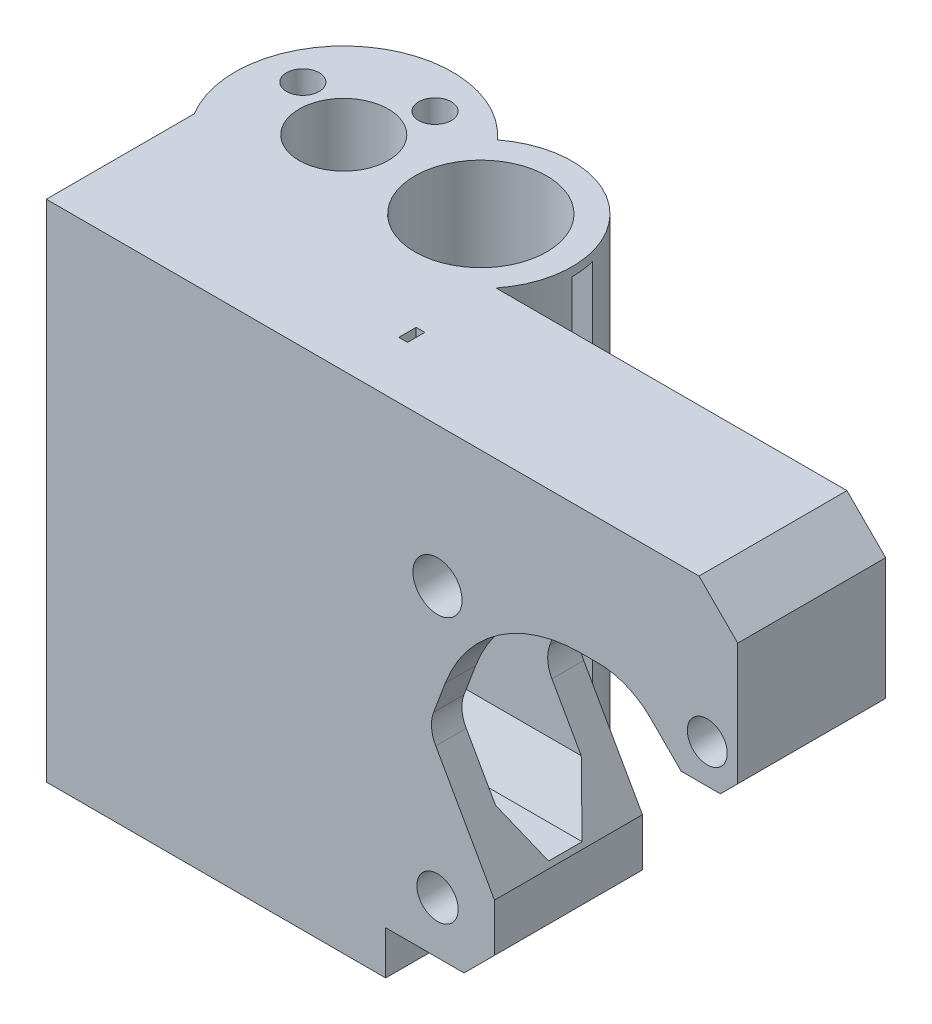
SolidWorks part; units mm, degrees
ref_plane "Front Plane" through (0, 0, 0) normal (0, 0, 1) x (1, 0, 0)
ref_plane "Top Plane" through (0, 0, 0) normal (0, 1, 0) x (1, 0, 0)
ref_plane "Right Plane" through (0, 0, 0) normal (1, 0, 0) x (0, 0, -1)
sketch "Sketch1" plane through (0, 0, 0) normal (0, 0, 1) x (1, 0, 0)
  line L0 (39, -53) -> (48, -53)
  line L1 (0, 0) -> (39, 0)
  line L2 (0, 0) -> (0, -58)
  line L3 (0, -58) -> (39, -58)
  line L4 (39, -53) -> (39, -58)
  line L5 (39, 0) -> (75, 0)
  line L6 (75, 0) -> (79.45, -4.45)
  line L7 (79.45, -4.45) -> (79.45, -18.45)
  line L8 (79.45, -18.45) -> (77.45, -20.45)
  line L9 (77.45, -20.45) -> (72.95, -20.45)
  line L10 (72.95, -20.45) -> (69.45, -16.95)
  line L12 (45.8405, -25.2376) -> (44.5009, -28.8048)
  line L13 (44.75, -32.0294) -> (51.5, -44)
  line L14 (51.5, -44) -> (51.5, -49.5)
  line L15 (61.4145, -14.45) -> (63.4145, -14.45)
  line L16 (51.5, -49.5) -> (48, -53)
  arc A5 (63.4145, -14.45) -> (69.45, -16.95) centre (63.4145, -22.9855) cw
  arc A6 (61.4145, -14.45) -> (45.8405, -25.2376) centre (61.4145, -31.0859) ccw
  arc A7 (44.5009, -28.8048) -> (44.75, -32.0294) centre (48.083, -30.15) ccw
  dimension "D1" = 58
  dimension "D2" = 39
  dimension "D3" = 75
  dimension "D4" = 4.45
  dimension "D5" = 135
  dimension "D6" = 14
  dimension "D7" = 2
  dimension "D8" = 3.5
  dimension "D9" = 6
  dimension "D10" = 5
  dimension "D11" = 4.5
  dimension "D12" = 130
  dimension "D13" = 3.5
  dimension "D14" = 5.5
  dimension "D15" = 6.75
  dimension "D16" = 9
  dimension "D17" = 13.85
  dimension "D18" = 3.417
  dimension "D19" = 2
extrude "Boss-Extrude1" add sketch "Sketch1" along normal blind 17
sketch "Sketch2" plane through (0, 0, 0) normal (0, 1, 0) x (1, 0, 0)
  line L0 (0, -17) -> (0, 6.5) construction
  line L1 (0, 6.5) -> (26.427, 6.5) construction
  circle A0 centre (26.427, 6.5) radius 10.5
  dimension "D2" = 21
  dimension "D1" = 23.5
  dimension "D3" = 26.427
extrude "Boss-Extrude2" add sketch "Sketch2" against normal up to surface (58 mm away) up to face at (19.5, -58, 8.5)
sketch "Sketch3" plane through (0, 0, 0) normal (0, 1, 0) x (1, 0, 0)
  line L0 (0, -17) -> (0, 20.4292) construction
  line L1 (10.6771, 6.5) -> (0, 6.5) construction
  line L2 (75, -17) -> (0, -17) construction
  circle A0 centre (10.6771, 6.5) radius 12.5
  dimension "D3" = 25
  dimension "D2" = 23.5
extrude "Boss-Extrude3" add sketch "Sketch3" against normal blind 13.5
sketch "Sketch4" plane through (0, 0, 0) normal (0, 1, 0) x (1, 0, 0)
  circle A0 centre (26.427, 6.5) radius 7.575
  circle A1 centre (10.6771, 6.5) radius 5.125
  dimension "D1" = 10.25
  dimension "D2" = 15.15
extrude "Cut-Extrude1" cut sketch "Sketch4" against normal through all
sketch "Sketch5" plane through (0, 0, 0) normal (-1, 0, 0) x (0, 0, 1)
  line L0 (10.5, -43.5) -> (6.65, -43.5)
  line L1 (6.65, -43.5) -> (3.65, -38)
  line L2 (3.65, -38) -> (3.65, -19)
  line L3 (3.65, -19) -> (6.65, -16)
  line L4 (6.65, -16) -> (10.5, -16)
  line L5 (10.5, -16) -> (13.5, -19)
  line L6 (13.5, -19) -> (13.5, -38)
  line L7 (13.5, -38) -> (10.5, -43.5)
  line L8 (17, 0) -> (0, 0) construction
  line L9 (17, 0) -> (17, -58) construction
  circle A0 centre (8.5, -6) radius 4.05
  circle A1 centre (8.5, -51) radius 4.05
  dimension "D8" = 8.1
  dimension "D9" = 8.1
  dimension "D1" = 19
  dimension "D2" = 3
  dimension "D3" = 3.85
  dimension "D4" = 16
  dimension "D5" = 6
  dimension "D6" = 51
  dimension "D7" = 5.5
  dimension "D10" = 3
  dimension "D11" = 3
  dimension "D12" = 19
  dimension "D13" = 3.85
  dimension "D14" = 3
  dimension "D15" = 3
  dimension "D16" = 3.5
  dimension "D17" = 8.5
  dimension "D18" = 8.5
extrude "Cut-Extrude2" cut sketch "Sketch5" against normal blind 35
sketch "Sketch6" plane through (0, 0, 0) normal (0, 0, -1) x (-1, 0, 0)
  line L0 (-75.9503, -16.0252) -> (-44.9503, -16.0252) construction
  line L1 (-44.9503, -16.0252) -> (-44.9503, -47.0252) construction
  line L2 (-44.9503, -47.0252) -> (-75.9503, -47.0252) construction
  line L3 (-75.9503, -47.0252) -> (-75.9503, -16.0252) construction
  line L4 (-75.9503, -31.5252) -> (-44.9503, -31.5252) construction
  line L5 (-60.4503, -16.0252) -> (-60.4503, -47.0252) construction
  circle A0 centre (-75.9503, -16.0252) radius 2.2933
  circle A1 centre (-44.9503, -16.0252) radius 2.8225
  circle A2 centre (-44.9503, -47.0252) radius 2.3733
  circle A3 centre (-60.4503, -31.5252) radius 11 construction
  point P14 (-60.4503, -31.5252)
  dimension "D3" = 22
  dimension "D1" = 31
  dimension "D2" = 31
extrude "Cut-Extrude3" cut sketch "Sketch6" against normal through all
sketch "Sketch8" plane through (35, 0, 0) normal (-1, 0, 0) x (0, 0, 1)
  line L8 (10.5, -43.5) -> (13.5, -38)
  line L9 (13.5, -38) -> (13.5, -19)
  line L10 (13.5, -19) -> (10.5, -16)
  line L11 (10.5, -16) -> (6.65, -16)
  line L12 (6.65, -16) -> (3.65, -19)
  line L13 (3.65, -19) -> (3.65, -38)
  line L14 (3.65, -38) -> (6.65, -43.5)
  line L15 (6.65, -43.5) -> (10.5, -43.5)
  line L16 (10.5, -43.5) -> (13.5, -38)
  line L17 (13.5, -38) -> (13.5, -19)
  line L18 (13.5, -19) -> (10.5, -16)
  line L19 (10.5, -16) -> (6.65, -16)
  line L20 (6.65, -16) -> (3.65, -19)
  line L21 (3.65, -19) -> (3.65, -38)
  line L22 (3.65, -38) -> (6.65, -43.5)
  line L23 (6.65, -43.5) -> (10.5, -43.5)
  dimension "D1" = 0
extrude "Cut-Extrude4" cut sketch "Sketch8" against normal blind 20
sketch "Sketch10" plane through (0, 0, 0) normal (0, 1, 0) x (1, 0, 0)
  line L0 (13.5702, 14.0925) -> (10.6771, 6.5) construction
  line L1 (10.6771, 6.5) -> (3.0846, 9.3931) construction
  circle A0 centre (13.5702, 14.0925) radius 1.875
  circle A1 centre (3.0846, 9.3931) radius 1.875
  dimension "D3" = 3.75
  dimension "D4" = 3.75
  dimension "D1" = 90
  dimension "D2" = 8.125
  dimension "D5" = 8.125
extrude "Cut-Extrude6" cut sketch "Sketch10" against normal through all
sketch "Sketch11" plane through (0, -58, 0) normal (0, -1, 0) x (1, 0, 0)
  line L0 (0, 17) -> (0, 0) construction
  line L1 (35, 8.5) -> (34, 8.5)
  line L2 (35, 8.5) -> (35, 10.5)
  line L3 (35, 10.5) -> (34, 10.5)
  line L4 (34, 8.5) -> (34, 10.5)
  line L5 (0, 17) -> (39, 17) construction
  dimension "D1" = 35
  dimension "D2" = 1
  dimension "D3" = 2
  dimension "D4" = 6.5
extrude "Cut-Extrude7" cut sketch "Sketch11" against normal blind 8
ref_plane "Plane1" through (0, -29, 0) normal (0, 1, 0) x (1, 0, 0)
mirror "Mirror1" about plane through (0, -29, 0) normal (0, 1, 0) of "Cut-Extrude7"
sketch "Sketch13" plane through (0, -58, 0) normal (0, -1, 0) x (1, 0, 0)
  line L0 (26.427, -6.5) -> (36.5692, -9.2176) construction
  line L1 (26.427, -6.5) -> (9.2701, -6.5) construction
  line L2 (26.427, -6.5) -> (36.927, -6.5) construction
  line L3 (33.7439, -8.4606) -> (36.5692, -9.2176)
  line L4 (36.927, -6.5) -> (34.002, -6.5)
  arc A0 (33.7439, -8.4606) -> (34.002, -6.5) centre (26.427, -6.5) ccw
  arc A1 (15.927, -6.5) -> (36.927, -6.5) centre (26.427, -6.5) ccw construction
  arc A2 (18.1808, 0) -> (34.6732, 0) centre (26.427, -6.5) ccw construction
  circle A3 centre (26.427, -6.5) radius 7.575 construction
  dimension "D1" = 15
  dimension "D2" = 180
extrude "Cut-Extrude9" cut sketch "Sketch13" against normal blind 57 and the other way through all
